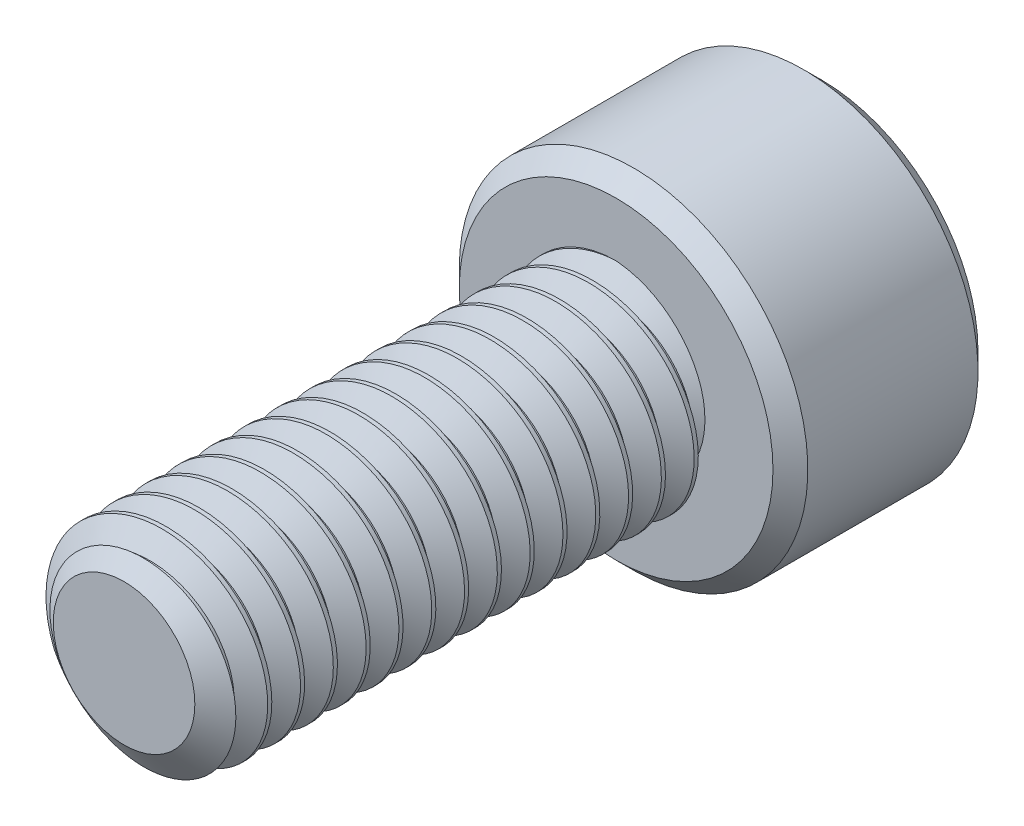
SolidWorks part; units mm, degrees
note: '?' marks a value the reader was unsure of.
other "DetailItem1"
ref_plane "Front Plane" through (0, 0, 0) normal (0, 0, 1) x (1, 0, 0)
ref_plane "Top Plane" through (0, 0, 0) normal (0, 1, 0) x (1, 0, 0)
ref_plane "Right Plane" through (0, 0, 0) normal (1, 0, 0) x (0, 0, -1)
sketch "Sketch1" plane through (0, 0, 0) normal (0, 0, 1) x (1, 0, 0)
  circle A0 centre (0, 0) radius 2.5
  dimension "OD" = 5
extrude "Extrude1" add sketch "Sketch1" against normal blind 12
sketch "Sketch2" plane through (0, 0, 0) normal (0, 0, 1) x (1, 0, 0)
  circle A0 centre (0, 0) radius 2.5 construction
  circle A1 centre (0, 0) radius 2.5
curve "Helix/Spiral1" pitch 0.8 height 12.8 turns 16 parameters "pitch"=0.8
sketch "Sketch3" plane through (0, 0, 0) normal (1, 0, 0) x (0, 0, -1)
  line L0 (-0.7, 2.5) -> (-0.4, 1.9804)
  line L1 (-0.4, 1.9804) -> (-0.3, 1.9804)
  line L2 (-0.3, 1.9804) -> (0, 2.5)
  line L3 (-0.7, 2.5) -> (0, 2.5)
  line L4 (-0.35, 2.5) -> (-0.35, 1.9804) construction
  line L5 (-0.55, 2.2402) -> (-0.15, 2.2402) construction
  line L6 (0, 2.5) -> (0, -2.5) construction
  dimension "D1" = 0.1
  dimension "D2" = 0.4
  dimension "D3" = 60
sweep "Cut-Sweep1" cut profiles "Sketch3" path "Helix/Spiral1"
sketch "Sketch4" plane through (0, 0, 0) normal (1, 0, 0) x (0, 0, -1)
  line L0 (0.5417, 2.5) -> (0, 1.7264)
  line L1 (0, 1.7264) -> (0, 2.5)
  line L2 (0.5417, 2.5) -> (0, 2.5)
  line L3 (-0.7, 2.5) -> (0, 2.5) construction
  line L4 (0, 0) -> (7.0209, 0) construction
  dimension "D1" = 55
  dimension "D2" = 0.254
revolve "Cut-Revolve1" cut sketch "Sketch4" angle 360 about L4
sketch "Sketch6" plane through (0, 0, -12) normal (0, 0, -1) x (-1, 0, 0)
  circle A0 centre (0, 0) radius 4.25
  dimension "head dia" = 8.5
extrude "Extrude2" add sketch "Sketch6" along normal blind 5
sketch "Sketch7" plane through (0, 0, -17) normal (0, 0, -1) x (-1, 0, 0)
  line L1 (0, 2.3094) -> (-2, 1.1547)
  line L2 (-2, 1.1547) -> (-2, -1.1547)
  line L3 (-2, -1.1547) -> (0, -2.3094)
  line L4 (0, -2.3094) -> (2, -1.1547)
  line L5 (2, -1.1547) -> (2, 1.1547)
  line L6 (2, 1.1547) -> (0, 2.3094)
  circle A0 centre (0, 0) radius 2 construction
  dimension "hex dia" = 4
extrude "Cut-Extrude1" cut sketch "Sketch7" against normal blind 3
sketch "Sketch8" plane through (0, 0, -17) normal (0, 0, -1) x (-1, 0, 0)
  circle A0 centre (0, 0) radius 2.3094
extrude "Cut-Extrude2" cut sketch "Sketch8" against normal through all draft 45
chamfer "Chamfer1" distance 0.425 angle 45 2 edges at (-4.25, 0, -17) (-4.25, 0, -12)
sketch "Sketch10" plane through (0, 0, -12) normal (0, 0, 1) x (1, 0, 0)
  circle A1 centre (0, 0) radius 2.5
  circle A2 centre (0, 0) radius 2.5
  dimension "D1" = 0
ref_plane "Plane1" through (0, 0, 0) normal (0, 0, 1) x (1, 0, 0)
extrude "partial thread" [suppressed] add sketch "Sketch10" along normal up to surface (13 mm away) separate body
chamfer "Chamfer2" [suppressed] distance 0.1 angle 45
combine bodies "Combine1" [suppressed] operation type? add bodies to combine 107 108
sketch "Sketch9" plane through (0, 0, 0) normal (1, 0, 0) x (0, 0, -1)
  line L0 (0, 2.5) -> (0, -2.5) construction
  line L1 (2, 2.5) -> (2, -2.5) construction
  dimension "D1" = 2
equation "\"D3@Helix/Spiral1\" = \"screw length@Extrude1\"+\"pitch@Helix/Spiral1\""
equation "\"D1@Sketch3\" = \"pitch@Helix/Spiral1\"*.125"
equation "\"D2@Sketch3\" = \"pitch@Helix/Spiral1\"*.5"
equation "\"D1@Cut-Extrude1\" = \"hex dia@Sketch7\"*.75"
equation "\"D1@Chamfer1\" = \"head dia@Sketch6\"*.05"
equation "\"D1@Sketch9\" = \"pitch@Helix/Spiral1\"*2.5"
equation "\"D1@Chamfer2\"=\"OD@Sketch1\"*.02"
